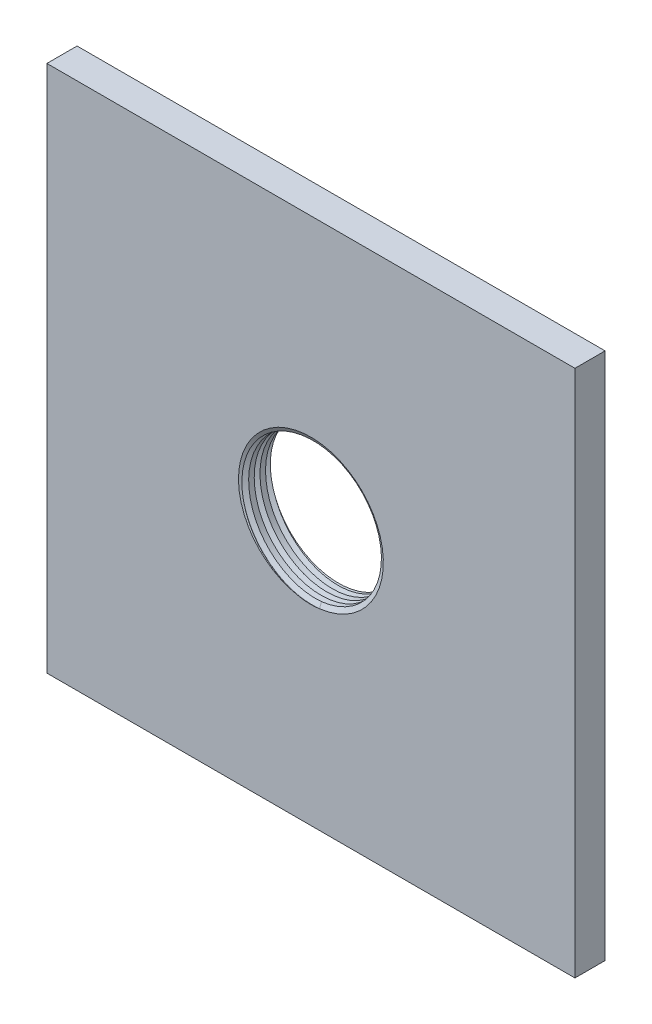
SolidWorks part; units mm, degrees
ref_plane "Front Plane" through (0, 0, 0) normal (0, 0, 1) x (1, 0, 0)
ref_plane "Top Plane" through (0, 0, 0) normal (0, 1, 0) x (1, 0, 0)
ref_plane "Right Plane" through (0, 0, 0) normal (1, 0, 0) x (0, 0, -1)
sketch "Sketch1" plane through (0, 0, 0) normal (0, 0, 1) x (1, 0, 0)
  line L1 (0, 0) -> (35, 0)
  line L2 (0, 0) -> (0, 35)
  line L3 (0, 35) -> (35, 35)
  line L4 (35, 0) -> (35, 35)
  dimension "D1" = 35
  dimension "D2" = 35
extrude "Boss-Extrude1" add sketch "Sketch1" along normal blind 2
sketch "Sketch2" plane through (0, 0, 2) normal (0, 0, 1) x (1, 0, 0)
  circle A0 centre (17.5, 17.5) radius 4.5
  dimension "D1" = 9
extrude "Cut-Extrude1" cut sketch "Sketch2" against normal up to next
sketch "Sketch21" plane through (0, 0, 2) normal (0, 0, 1) x (1, 0, 0)
  circle A0 centre (17.5, 17.5) radius 4.5 construction
  circle A1 centre (17.5, 17.5) radius 4.5
curve "Helix/Spiral8" pitch 0.75 height 2.25 radius 4.5 centre (17.5, 17.5, 2) axis (0, 0, -1) start towards (1, 0, 0)
ref_plane "Plane5" through (0, 17.5, 0) normal (0, -1, 0) x (-1, 0, 0)
sketch "Sketch22" plane through (0, 17.5, 0) normal (0, -1, 0) x (-1, 0, 0)
  line L0 (-35, -2) -> (-35, 0) construction
  line L1 (-22, -2.3822) -> (-22, -2)
  line L2 (-22, -2) -> (-22.301, -2.1738)
  line L3 (-22.301, -2.2084) -> (-22, -2.3822)
  line L4 (-22.2207, -2.1911) -> (-22.2207, -2.2548) construction
  line L5 (-22.2207, -2.1911) -> (-22.2207, -2.1274) construction
  line L7 (-22, -2.1911) -> (-22.311, -2.1911) construction
  circle A0 centre (-22.1103, -2.1911) radius 0.1103 construction
  arc A1 (-22.301, -2.2084) -> (-22.301, -2.1738) centre (-22.291, -2.1911) cw
  dimension "D2" = 0.02
  dimension "D1" = 0.311
sweep "Cut-Sweep9" cut profiles "Sketch22" path "Helix/Spiral8"
sketch "Sketch24" plane through (0, 0, 2) normal (0, 0, 1) x (1, 0, 0)
  circle A0 centre (17.5, 17.5) radius 4.801
extrude "Cut-Extrude2" cut sketch "Sketch24" against normal blind 10 draft 60
sketch "Sketch25" plane through (0, 0, 0) normal (0, 0, -1) x (-1, 0, 0)
  circle A0 centre (-17.5, 17.5) radius 4.801
extrude "Cut-Extrude3" cut sketch "Sketch25" against normal blind 10 draft 60
